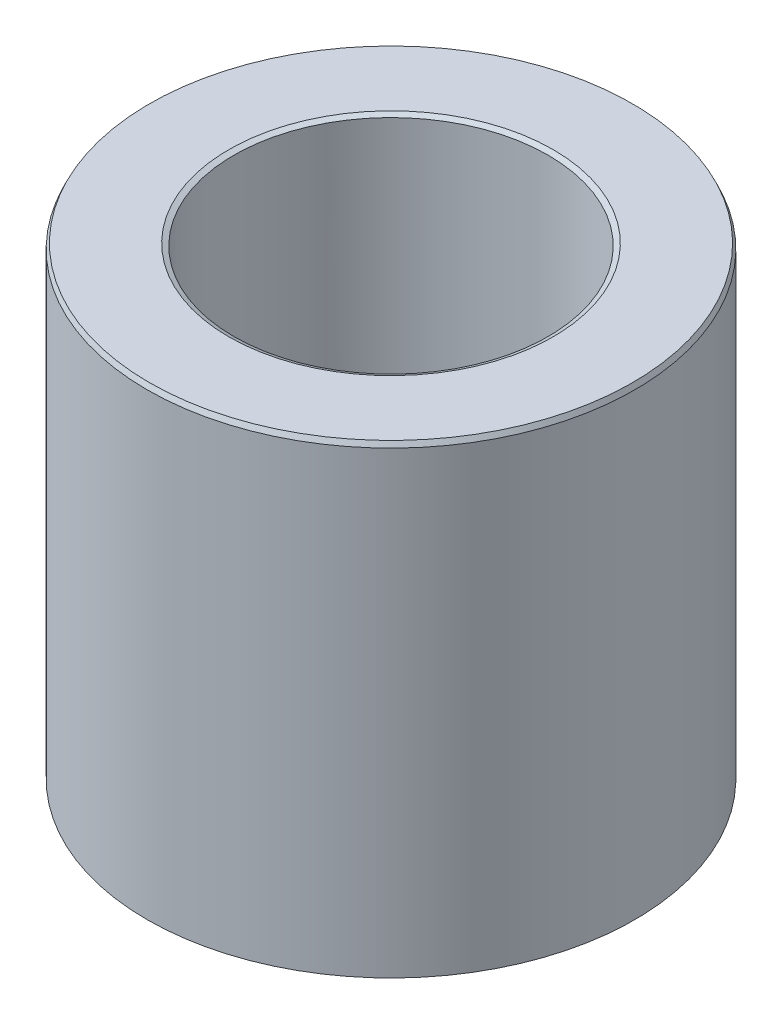
SolidWorks part; units mm, degrees
ref_plane "Front Plane" through (0, 0, 0) normal (0, 0, 1) x (1, 0, 0)
ref_plane "Top Plane" through (0, 0, 0) normal (0, 1, 0) x (1, 0, 0)
ref_plane "Right Plane" through (0, 0, 0) normal (1, 0, 0) x (0, 0, -1)
sketch "Sketch1" plane through (0, 0, 0) normal (0, 1, 0) x (1, 0, 0)
  circle A0 centre (0, 0) radius 37.5
  dimension "SLEEVE_OD" = 75
extrude "Boss-Extrude1" add sketch "Sketch1" along normal blind 71.7026
sketch "Sketch2" plane through (0, 0, 0) normal (0, 1, 0) x (1, 0, 0)
  circle A0 centre (0, 0) radius 24.1663
  dimension "BORE_D" = 48.3326
extrude "Cut-Extrude1" cut sketch "Sketch2" along normal through all
chamfer "Chamfer1" distance 0.7756 angle 24.419 4 edges at (0, 71.7026, 24.1663) (0, 0, 24.1663) (0, 0, 37.5) (0, 71.7026, 37.5) first distance on face at (0, 71.7026, 24.1663) first distance on face at (0, 0, 24.1663) first distance on face at (0, 71.7026, 37.5)
